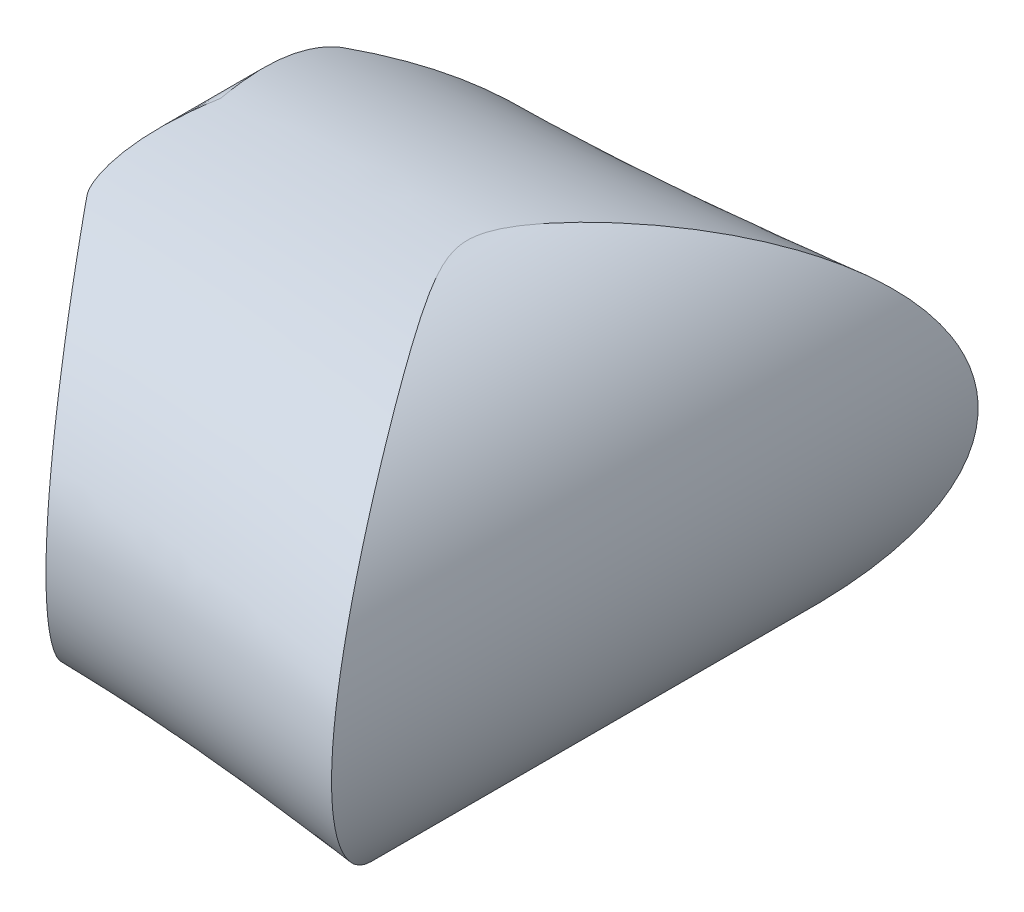
SolidWorks part; units mm, degrees
ref_plane "Front Plane" through (0, 0, 0) normal (0, 0, 1) x (1, 0, 0)
ref_plane "Top Plane" through (0, 0, 0) normal (0, 1, 0) x (1, 0, 0)
ref_plane "Right Plane" through (0, 0, 0) normal (1, 0, 0) x (0, 0, -1)
sketch "Sketch1" plane through (0, 0, 0) normal (1, 0, 0) x (0, 0, -1)
  line L0 (-1000, 0) -> (49000, 0) construction
  ellipse E0 centre (0, 0) end of major axis (-134.62, 0) minor radius 100.33
  dimension "D1" = 200.66
  dimension "D2" = 269.24
ref_plane "Plane1" through (252.73, 0, 0) normal (1, 0, 0) x (0, 0, -1)
ref_plane "Plane2" through (100.33, 0, 0) normal (1, 0, 0) x (0, 0, -1)
sketch "Sketch5" plane through (100.33, 0, 0) normal (1, 0, 0) x (0, 0, -1)
  line L0 (-1000, 0) -> (49000, 0) construction
  ellipse E0 centre (0, 0) end of major axis (134.62, 0) minor radius 100.33
  dimension "D1" = 200.66
  dimension "D2" = 269.24
sketch "Sketch2" plane through (252.73, 0, 0) normal (1, 0, 0) x (0, 0, -1)
  line L0 (-1000, 0) -> (49000, 0) construction
  line L1 (-201000, 0) -> (249000, 0) construction
  ellipse E0 centre (0, 0) end of major axis (-152.4, 0) minor radius 101.6
  dimension "D1" = 203.2
  dimension "D2" = 304.8
loft "Loft1" add profiles "Sketch1", "Sketch5", "Sketch2" connector at (0, 74.3343, -90.4131) connector at (100.33, 72.5857, -92.9357) connector at (252.73, 75.4465, -102.0703)
sketch "Sketch3" plane through (0, 0, 0) normal (0, 0, 1) x (1, 0, 0)
  line L0 (0, -984.6591) -> (0, 49015.3409) construction
  line L2 (0, 0) -> (57.885, 100.2597) construction
  line L3 (-1000, 0) -> (49000, 0) construction
  line L4 (0, 0) -> (57.885, -100.2597) construction
  line L5 (100.33, -55) -> (100.33, 55) construction
  line L6 (0, -100.33) -> (0, -110.2613)
  line L7 (0, 100.33) -> (0, 110.2613)
  line L9 (0, 100.3301) -> (0, -100.3301) construction
  line L10 (0, 110.2613) -> (48.0012, 110.2613)
  line L11 (48.0012, 110.2613) -> (48.0012, 100.2613)
  line L12 (100.33, -1031.9324) -> (100.33, 48968.0676) construction
  line L13 (0, -110.2613) -> (47.9987, -110.2613)
  line L14 (47.9987, -110.2613) -> (47.9987, -100.2613)
  arc A0 (0, 100.33) -> (0, -100.33) centre (0, 0) ccw
  arc A1 (45.4148, -89.4629) -> (47.9987, -100.2613) centre (47.9987, -94.5529) ccw
  arc A2 (48.0012, 100.2613) -> (45.4148, 89.4629) centre (47.9987, 94.5529) ccw
  arc A3 (45.4148, -89.4629) -> (45.4148, 89.4629) centre (0, 0) ccw
  spline S50 degree 3 poles (252.73, 101.6001) (249.7653, 101.5667) (244.1791, 101.5036) (236.5126, 101.4183) (230.2478, 101.3495) (224.0243, 101.282) (218.3803, 101.2218) (212.9061, 101.1645) (208.6096, 101.1201) (204.7226, 101.0806) (201.1982, 101.0453) (197.4969, 101.0087) (193.5891, 100.9707) (188.7754, 100.9248) (184.6195, 100.8862) (180.964, 100.8529) (177.7041, 100.8237) (173.825, 100.7897) (169.9053, 100.7562) (166.4887, 100.7277) (162.7437, 100.6972) (157.9514, 100.6592) (152.9161, 100.6211) (148.9524, 100.5923) (145.6167, 100.5687) (141.9221, 100.5433) (137.6971, 100.5156) (132.7425, 100.4846) (127.2134, 100.4521) (120.3795, 100.4151) (113.0123, 100.3795) (105.9255, 100.3498) (99.2251, 100.3257) (93.8522, 100.3095) (89.5775, 100.2986) (86.4129, 100.2913) (83.0267, 100.2843) (79.2282, 100.2776) (74.6289, 100.2709) (70.1413, 100.2659) (65.2431, 100.2622) (61.4746, 100.2605) (58.2386, 100.2597) (55.2047, 100.2595) (51.6429, 100.2599) (48.0791, 100.2612) (45.1415, 100.2627) (41.4906, 100.2651) (37.3345, 100.2688) (32.6272, 100.2739) (28.4844, 100.2792) (23.454, 100.2864) (17.8785, 100.2955) (11.9195, 100.3063) (6.0397, 100.3176) (2.0861, 100.3258) (0, 100.3301) knots 0 0 0 0 0.035194 0.066313 0.091009 0.109562 0.140191 0.158008 0.174545 0.191194 0.204149 0.216382 0.235131 0.250537 0.273523 0.284464 0.29393 0.31222 0.330511 0.340459 0.352777 0.374966 0.397346 0.412548 0.422017 0.436942 0.456404 0.472169 0.495756 0.522036 0.553289 0.583207 0.606157 0.632824 0.646984 0.656898 0.670388 0.687179 0.701986 0.724983 0.740447 0.760128 0.769715 0.778858 0.796141 0.811995 0.82116 0.831011 0.855331 0.870494 0.886888 0.904505 0.930206 0.95307 0.975238 1 1 1 1 construction
  spline S51 degree 3 poles (0, -100.3301) (3.1163, -100.3237) (8.715, -100.3122) (16.3971, -100.298) (22.5309, -100.2879) (28.6545, -100.2788) (34.2364, -100.2719) (39.4301, -100.2669) (43.1463, -100.264) (46.4824, -100.2619) (50.1517, -100.2603) (53.7311, -100.2596) (56.922, -100.2596) (59.9458, -100.26) (63.5548, -100.2613) (67.2297, -100.2636) (70.5981, -100.2666) (74.3241, -100.2706) (79.0584, -100.2771) (83.5565, -100.2853) (86.6043, -100.2918) (88.3516, -100.2957) (90.7631, -100.3015) (94.429, -100.3113) (98.7357, -100.3245) (102.8828, -100.3388) (107.0779, -100.3547) (111.6856, -100.374) (117.4341, -100.4006) (123.6415, -100.4323) (129.4969, -100.4653) (134.6064, -100.4961) (139.2434, -100.5255) (143.5126, -100.5541) (146.8424, -100.5773) (150.4231, -100.6028) (155.1995, -100.6381) (161.3092, -100.6855) (166.9176, -100.7311) (172.0828, -100.7747) (176.9335, -100.8168) (183.3711, -100.8744) (189.2128, -100.9288) (194.1552, -100.9762) (198.2794, -101.0163) (203.2223, -101.0654) (209.6041, -101.1302) (214.931, -101.1856) (219.8694, -101.2377) (223.2389, -101.2737) (226.2713, -101.3064) (229.0413, -101.3365) (232.0142, -101.3689) (236.0733, -101.4136) (240.9211, -101.4673) (246.7876, -101.533) (250.7558, -101.5778) (252.73, -101.6001) knots 0 0 0 0 0.036991 0.066457 0.091188 0.109799 0.139144 0.157446 0.171449 0.183256 0.197046 0.215004 0.225744 0.234923 0.250896 0.268582 0.278544 0.290879 0.31281 0.334742 0.344271 0.348988 0.355482 0.372897 0.392502 0.406603 0.422124 0.442298 0.461298 0.49036 0.515981 0.530804 0.551012 0.571024 0.581481 0.590538 0.613528 0.638178 0.663063 0.680103 0.699491 0.720644 0.75652 0.768837 0.779313 0.805477 0.827512 0.855069 0.868711 0.886135 0.895068 0.904708 0.919017 0.930359 0.952893 0.976565 1 1 1 1 construction
  spline S59 degree 3 poles (0, -100.3301) (3.1163, -100.3237) (8.715, -100.3122) (16.3971, -100.298) (22.5309, -100.2879) (28.6545, -100.2788) (34.2364, -100.2719) (39.4301, -100.2669) (43.1463, -100.264) (46.4824, -100.2619) (50.1517, -100.2603) (53.7311, -100.2596) (56.922, -100.2596) (59.9458, -100.26) (63.5548, -100.2613) (67.2297, -100.2636) (70.5981, -100.2666) (74.3241, -100.2706) (79.0584, -100.2771) (83.5565, -100.2853) (86.6043, -100.2918) (88.3516, -100.2957) (90.7631, -100.3015) (94.429, -100.3113) (98.7357, -100.3245) (102.8828, -100.3388) (107.0779, -100.3547) (111.6856, -100.374) (117.4341, -100.4006) (123.6415, -100.4323) (129.4969, -100.4653) (134.6064, -100.4961) (139.2434, -100.5255) (143.5126, -100.5541) (146.8424, -100.5773) (150.4231, -100.6028) (155.1995, -100.6381) (161.3092, -100.6855) (166.9176, -100.7311) (172.0828, -100.7747) (176.9335, -100.8168) (183.3711, -100.8744) (189.2128, -100.9288) (194.1552, -100.9762) (198.2794, -101.0163) (203.2223, -101.0654) (209.6041, -101.1302) (214.931, -101.1856) (219.8694, -101.2377) (223.2389, -101.2737) (226.2713, -101.3064) (229.0413, -101.3365) (232.0142, -101.3689) (236.0733, -101.4136) (240.9211, -101.4673) (246.7876, -101.533) (250.7558, -101.5778) (252.73, -101.6001) knots 0 0 0 0 0.036991 0.066457 0.091188 0.109799 0.139144 0.157446 0.171449 0.183256 0.197046 0.215004 0.225744 0.234923 0.250896 0.268582 0.278544 0.290879 0.31281 0.334742 0.344271 0.348988 0.355482 0.372897 0.392502 0.406603 0.422124 0.442298 0.461298 0.49036 0.515981 0.530804 0.551012 0.571024 0.581481 0.590538 0.613528 0.638178 0.663063 0.680103 0.699491 0.720644 0.75652 0.768837 0.779313 0.805477 0.827512 0.855069 0.868711 0.886135 0.895068 0.904708 0.919017 0.930359 0.952893 0.976565 1 1 1 1 construction
  spline S80 degree 3 poles (252.73, 101.6001) (249.7653, 101.5667) (244.1791, 101.5036) (236.5126, 101.4183) (230.2478, 101.3495) (224.0243, 101.282) (218.3803, 101.2218) (212.9061, 101.1645) (208.6096, 101.1201) (204.7226, 101.0806) (201.1982, 101.0453) (197.4969, 101.0087) (193.5891, 100.9707) (188.7754, 100.9248) (184.6195, 100.8862) (180.964, 100.8529) (177.7041, 100.8237) (173.825, 100.7897) (169.9053, 100.7562) (166.4887, 100.7277) (162.7437, 100.6972) (157.9514, 100.6592) (152.9161, 100.6211) (148.9524, 100.5923) (145.6167, 100.5687) (141.9221, 100.5433) (137.6971, 100.5156) (132.7425, 100.4846) (127.2134, 100.4521) (120.3795, 100.4151) (113.0123, 100.3795) (105.9255, 100.3498) (99.2251, 100.3257) (93.8522, 100.3095) (89.5775, 100.2986) (86.4129, 100.2913) (83.0267, 100.2843) (79.2282, 100.2776) (74.6289, 100.2709) (70.1413, 100.2659) (65.2431, 100.2622) (61.4746, 100.2605) (58.2386, 100.2597) (55.2047, 100.2595) (51.6429, 100.2599) (48.0791, 100.2612) (45.1415, 100.2627) (41.4906, 100.2651) (37.3345, 100.2688) (32.6272, 100.2739) (28.4844, 100.2792) (23.454, 100.2864) (17.8785, 100.2955) (11.9195, 100.3063) (6.0397, 100.3176) (2.0861, 100.3258) (0, 100.3301) knots 0 0 0 0 0.035194 0.066313 0.091009 0.109562 0.140191 0.158008 0.174545 0.191194 0.204149 0.216382 0.235131 0.250537 0.273523 0.284464 0.29393 0.31222 0.330511 0.340459 0.352777 0.374966 0.397346 0.412548 0.422017 0.436942 0.456404 0.472169 0.495756 0.522036 0.553289 0.583207 0.606157 0.632824 0.646984 0.656898 0.670388 0.687179 0.701986 0.724983 0.740447 0.760128 0.769715 0.778858 0.796141 0.811995 0.82116 0.831011 0.855331 0.870494 0.886888 0.904505 0.930206 0.95307 0.975238 1 1 1 1 construction
  spline S101 degree 3 poles (252.73, 101.6001) (249.7653, 101.5667) (244.1791, 101.5036) (236.5126, 101.4183) (230.2478, 101.3495) (224.0243, 101.282) (218.3803, 101.2218) (212.9061, 101.1645) (208.6096, 101.1201) (204.7226, 101.0806) (201.1982, 101.0453) (197.4969, 101.0087) (193.5891, 100.9707) (188.7754, 100.9248) (184.6195, 100.8862) (180.964, 100.8529) (177.7041, 100.8237) (173.825, 100.7897) (169.9053, 100.7562) (166.4887, 100.7277) (162.7437, 100.6972) (157.9514, 100.6592) (152.9161, 100.6211) (148.9524, 100.5923) (145.6167, 100.5687) (141.9221, 100.5433) (137.6971, 100.5156) (132.7425, 100.4846) (127.2134, 100.4521) (120.3795, 100.4151) (113.0123, 100.3795) (105.9255, 100.3498) (99.2251, 100.3257) (93.8522, 100.3095) (89.5775, 100.2986) (86.4129, 100.2913) (83.0267, 100.2843) (79.2282, 100.2776) (74.6289, 100.2709) (70.1413, 100.2659) (65.2431, 100.2622) (61.4746, 100.2605) (58.2386, 100.2597) (55.2047, 100.2595) (51.6429, 100.2599) (48.0791, 100.2612) (45.1415, 100.2627) (41.4906, 100.2651) (37.3345, 100.2688) (32.6272, 100.2739) (28.4844, 100.2792) (23.454, 100.2864) (17.8785, 100.2955) (11.9195, 100.3063) (6.0397, 100.3176) (2.0861, 100.3258) (0, 100.3301) knots 0 0 0 0 0.035194 0.066313 0.091009 0.109562 0.140191 0.158008 0.174545 0.191194 0.204149 0.216382 0.235131 0.250537 0.273523 0.284464 0.29393 0.31222 0.330511 0.340459 0.352777 0.374966 0.397346 0.412548 0.422017 0.436942 0.456404 0.472169 0.495756 0.522036 0.553289 0.583207 0.606157 0.632824 0.646984 0.656898 0.670388 0.687179 0.701986 0.724983 0.740447 0.760128 0.769715 0.778858 0.796141 0.811995 0.82116 0.831011 0.855331 0.870494 0.886888 0.904505 0.930206 0.95307 0.975238 1 1 1 1 construction
  dimension "D4" = 10
  dimension "D1" = 30
  dimension "D2" = 30
  dimension "D3" = 10
sketch "Sketch4" plane through (0, 0, 0) normal (0, 0, 1) x (1, 0, 0)
  line L0 (-1000, 0) -> (49000, 0) construction
  line L1 (252.73, -101.6001) -> (252.73, 101.6001) construction
  line L2 (151.13, 101.6) -> (151.13, 111.6)
  line L3 (151.13, 111.6) -> (262.73, 111.6)
  line L4 (262.73, 111.6) -> (262.73, -111.6)
  line L5 (262.73, -111.6) -> (151.13, -111.6)
  line L6 (151.13, -111.6) -> (151.13, -101.6)
  arc A0 (151.13, -101.6) -> (151.13, 101.6) centre (151.13, 0) ccw
  dimension "D1" = 203.2
  dimension "D2" = 10
  dimension "D3" = 10
  dimension "D4" = 10
extrude "Cut-Extrude2" cut sketch "Sketch4" against normal through all and the other way through all
extrude "Cut-Extrude8" cut sketch "Sketch3" against normal through all and the other way through all
sketch3d "3DSketch2"
  line L0 (-127, 0, 0) -> (381, 0, 0)
  line L1 (0, 0, -190.5) -> (0, 0, 190.5)
  line L2 (151.13, 0, -190.5) -> (151.13, 0, 190.5)
  point P3 (0, 0, 0)
  point P4 (0, 0, 0)
  point P9 (151.13, 0, 0)
  point P10 (0, 0, 0)
  dimension "D1" = 508
  dimension "D2" = 127
  dimension "D3" = 151.13
  dimension "D4" = 381
